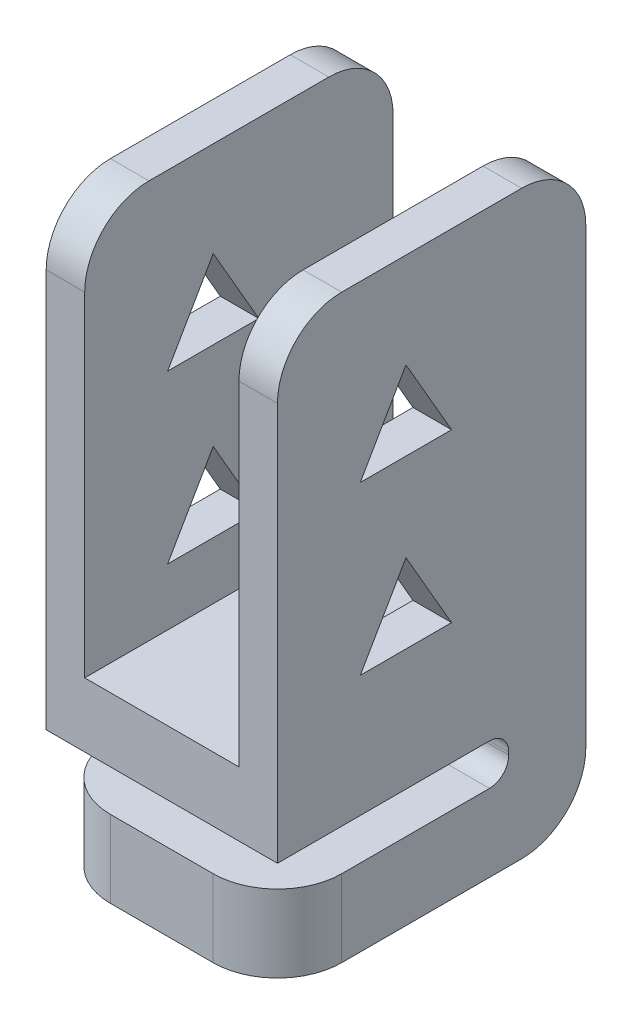
SolidWorks part; units mm, degrees
material "ABS"
ref_plane "Front Plane" through (0, 0, 0) normal (0, 0, 1) x (1, 0, 0)
ref_plane "Top Plane" through (0, 0, 0) normal (0, 1, 0) x (1, 0, 0)
ref_plane "Right Plane" through (0, 0, 0) normal (1, 0, 0) x (0, 0, -1)
sketch "Sketch2" plane through (0, 0, 0) normal (1, 0, 0) x (0, 0, -1)
  line L0 (3, -9) -> (3, -10.6)
  line L1 (-6, 9) -> (6, 9)
  line L2 (-6, 9) -> (-6, -9)
  line L3 (-6, -9) -> (3, -9)
  line L4 (6, 9) -> (6, -9)
  line L5 (-6, 9) -> (6, -9) construction
  line L6 (-6, -9) -> (6, 9) construction
  line L7 (3, -10.6) -> (-6, -10.6)
  line L8 (-6, -10.6) -> (-6, -13.6)
  line L9 (-6, -13.6) -> (6, -13.6)
  line L10 (6, -13.6) -> (6, -9)
  line L11 (3, -9) -> (6, -9) construction
  point P0 (0, 0)
  dimension "D1" = 1.6
  dimension "D2" = 18
  dimension "D3" = 12
  dimension "D4" = 3
  dimension "D6" = 3
extrude "Boss-Extrude1" add sketch "Sketch2" along normal mid plane 9
sketch "Sketch3" plane through (0, 0, 6) normal (0, 0, 1) x (1, 0, 0)
  line L0 (-4.5, 9) -> (-4.5, -9) construction
  line L1 (-3, 6.5) -> (3, 6.5) construction
  line L2 (-3, 6.5) -> (-3, -6.5)
  line L3 (-3, -6.5) -> (3, -6.5)
  line L4 (3, 6.5) -> (3, -6.5)
  line L5 (-3, 6.5) -> (3, -6.5) construction
  line L6 (-3, -6.5) -> (3, 6.5) construction
  line L7 (4.5, 9) -> (-4.5, 9) construction
  line L8 (-3, 6.5) -> (-3, 9)
  line L9 (-3, 9) -> (3, 9)
  line L10 (3, 9) -> (3, 6.5)
  point P0 (0, 0)
  point P7 (-4.5, 0)
  point P10 (0, 9)
  dimension "D1" = 6
  dimension "D2" = 13
extrude "Cut-Extrude1" cut sketch "Sketch3" against normal up to surface (12 mm away) up to face at (0, -2.3, -6)
sketch "Sketch4" plane through (0, 0, 0) normal (1, 0, 0) x (0, 0, -1)
  line L1 (0.7754, 2.225) -> (-1, 5.3)
  line L2 (-1, 5.3) -> (-2.7754, 2.225)
  line L3 (-2.7754, 2.225) -> (0.7754, 2.225)
  line L4 (0.7754, -4.275) -> (-1, -1.2)
  line L5 (-1, -1.2) -> (-2.7754, -4.275)
  line L6 (-2.7754, -4.275) -> (0.7754, -4.275)
  circle A0 centre (-1, 3.25) radius 1.025 construction
  circle A1 centre (-1, -3.25) radius 1.025 construction
  circle A2 centre (-1, -3.25) radius 1.025 construction
  circle A3 centre (-1, 3.25) radius 1.025 construction
  circle A4 centre (-1, 3.25) radius 1.025 construction
  circle A5 centre (-1, -3.25) radius 1.025 construction
extrude "Cut-Extrude2" cut sketch "Sketch4" against normal through all and the other way through all
fillet "Fillet1" radius 2.5 7 edges at (0, -13.6, -6) (-3.75, 9, -6) (3.75, 9, -6) (-3.75, 9, 6) (3.75, 9, 6) (4.5, -12.1, 6) (-4.5, -12.1, 6)
fillet "Fillet2" radius 0.75 2 edges at (0, -10.6, -3) (0, -9, -3)
